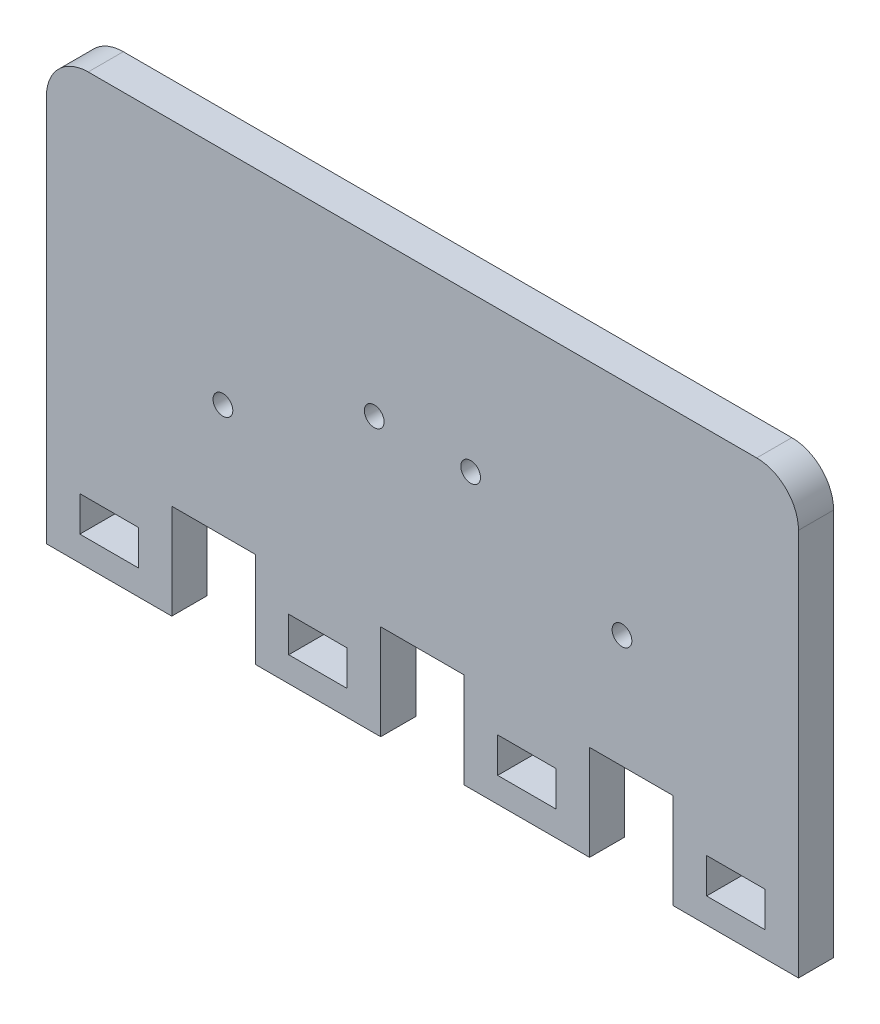
SolidWorks part; units mm, degrees
material "Teak"
ref_plane "Front Plane" through (0, 0, 0) normal (0, 0, 1) x (1, 0, 0)
ref_plane "Top Plane" through (0, 0, 0) normal (0, 1, 0) x (1, 0, 0)
ref_plane "Right Plane" through (0, 0, 0) normal (1, 0, 0) x (0, 0, -1)
sketch "Sketch1" plane through (0, 0, 0) normal (0, 0, 1) x (1, 0, 0)
  line L1 (-30.5325, 25.3111) -> (83.7675, 25.3111)
  line L2 (-30.5325, 25.3111) -> (-30.5325, -30.8229)
  line L3 (-30.5325, -30.8229) -> (83.7675, -30.8229)
  line L4 (83.7675, 25.3111) -> (83.7675, -30.8229)
  dimension "D1" = 56.134
  dimension "D2" = 114.3
extrude "Boss-Extrude1" add sketch "Sketch1" along normal blind 5.334 contours L1 L4 L3 L2
sketch "Sketch2" plane through (0, 0, 5.334) normal (0, 0, 1) x (1, 0, 0)
  line L0 (-30.5325, -30.8229) -> (83.7675, -30.8229) construction
  line L1 (-11.4825, -30.8229) -> (1.2175, -30.8229)
  line L2 (-11.4825, -30.8229) -> (-11.4825, -25.4889)
  line L3 (-11.4825, -25.4889) -> (1.2175, -25.4889)
  line L4 (1.2175, -30.8229) -> (1.2175, -25.4889)
  line L5 (-11.4825, -25.4889) -> (-30.5325, -25.4889) construction
  line L6 (20.2675, -30.8229) -> (32.9675, -30.8229)
  line L7 (20.2675, -30.8229) -> (20.2675, -25.4889)
  line L8 (20.2675, -25.4889) -> (32.9675, -25.4889)
  line L9 (32.9675, -30.8229) -> (32.9675, -25.4889)
  line L10 (52.0175, -30.8229) -> (64.7175, -30.8229)
  line L11 (52.0175, -30.8229) -> (52.0175, -25.4889)
  line L12 (52.0175, -25.4889) -> (64.7175, -25.4889)
  line L13 (64.7175, -30.8229) -> (64.7175, -25.4889)
  line L14 (-30.5325, 25.3111) -> (-30.5325, -30.8229) construction
  line L15 (1.2175, -25.4889) -> (20.2675, -25.4889) construction
  line L16 (32.9675, -25.4889) -> (52.0175, -25.4889) construction
  line L17 (64.7175, -25.4889) -> (83.7675, -25.4889) construction
  line L18 (83.7675, 25.3111) -> (83.7675, -30.8229) construction
  dimension "D1" = 19.05
  dimension "D3" = 19.05
  dimension "D5" = 19.05
  dimension "D6" = 12.7
  dimension "D7" = 19.05
  dimension "D8" = 5.334
extrude "Cut-Extrude1" cut sketch "Sketch2" against normal through all
fillet "Fillet1" radius 6.35 2 edges at (83.7675, 25.3111, 2.667) (-30.5325, 25.3111, 2.667)
sketch "Sketch3" plane through (0, 0, 0) normal (0, 0, -1) x (-1, 0, 0)
  line L16 (24.1825, 25.3111) -> (-77.4175, 25.3111)
  line L17 (-83.7675, 18.9611) -> (-83.7675, -30.8229)
  line L18 (-83.7675, -30.8229) -> (-64.7175, -30.8229)
  line L19 (-64.7175, -30.8229) -> (-64.7175, -25.4889)
  line L20 (-64.7175, -25.4889) -> (-52.0175, -25.4889)
  line L21 (-52.0175, -25.4889) -> (-52.0175, -30.8229)
  line L22 (-52.0175, -30.8229) -> (-32.9675, -30.8229)
  line L23 (-32.9675, -30.8229) -> (-32.9675, -25.4889)
  line L24 (-32.9675, -25.4889) -> (-20.2675, -25.4889)
  line L25 (-20.2675, -25.4889) -> (-20.2675, -30.8229)
  line L26 (-20.2675, -30.8229) -> (-1.2175, -30.8229)
  line L27 (-1.2175, -30.8229) -> (-1.2175, -25.4889)
  line L28 (-1.2175, -25.4889) -> (11.4825, -25.4889)
  line L29 (11.4825, -25.4889) -> (11.4825, -30.8229)
  line L30 (11.4825, -30.8229) -> (30.5325, -30.8229)
  line L31 (30.5325, -30.8229) -> (30.5325, 18.9611)
  line L32 (24.1825, 25.3111) -> (-77.4175, 25.3111)
  line L33 (-83.7675, 18.9611) -> (-83.7675, -30.8229)
  line L34 (-83.7675, -30.8229) -> (-64.7175, -30.8229)
  line L35 (-64.7175, -30.8229) -> (-64.7175, -25.4889)
  line L36 (-64.7175, -25.4889) -> (-52.0175, -25.4889)
  line L37 (-52.0175, -25.4889) -> (-52.0175, -30.8229)
  line L38 (-52.0175, -30.8229) -> (-32.9675, -30.8229)
  line L39 (-32.9675, -30.8229) -> (-32.9675, -25.4889)
  line L40 (-32.9675, -25.4889) -> (-20.2675, -25.4889)
  line L41 (-20.2675, -25.4889) -> (-20.2675, -30.8229)
  line L42 (-20.2675, -30.8229) -> (-1.2175, -30.8229)
  line L43 (-1.2175, -30.8229) -> (-1.2175, -25.4889)
  line L44 (-1.2175, -25.4889) -> (11.4825, -25.4889)
  line L45 (11.4825, -25.4889) -> (11.4825, -30.8229)
  line L46 (11.4825, -30.8229) -> (30.5325, -30.8229)
  line L47 (30.5325, -30.8229) -> (30.5325, 18.9611)
  line L48 (-83.7675, 18.9611) -> (-83.7675, -30.8229)
  line L49 (24.1825, 25.3111) -> (-77.4175, 25.3111)
  line L50 (30.5325, -30.8229) -> (30.5325, 18.9611)
  line L51 (11.4825, -30.8229) -> (30.5325, -30.8229)
  line L52 (11.4825, -25.4889) -> (11.4825, -30.8229)
  line L53 (-1.2175, -25.4889) -> (11.4825, -25.4889)
  line L54 (-1.2175, -30.8229) -> (-1.2175, -25.4889)
  line L55 (-20.2675, -30.8229) -> (-1.2175, -30.8229)
  line L56 (-20.2675, -25.4889) -> (-20.2675, -30.8229)
  line L57 (-32.9675, -25.4889) -> (-20.2675, -25.4889)
  line L58 (-32.9675, -30.8229) -> (-32.9675, -25.4889)
  line L59 (-52.0175, -30.8229) -> (-32.9675, -30.8229)
  line L60 (-52.0175, -25.4889) -> (-52.0175, -30.8229)
  line L61 (-64.7175, -25.4889) -> (-52.0175, -25.4889)
  line L62 (-64.7175, -30.8229) -> (-64.7175, -25.4889)
  line L63 (-83.7675, -30.8229) -> (-64.7175, -30.8229)
  line L64 (-83.7675, 18.9611) -> (-83.7675, -30.8229)
  line L65 (24.1825, 25.3111) -> (-77.4175, 25.3111)
  line L66 (30.5325, -30.8229) -> (30.5325, 18.9611)
  line L67 (11.4825, -30.8229) -> (30.5325, -30.8229)
  line L68 (11.4825, -25.4889) -> (11.4825, -30.8229)
  line L69 (-1.2175, -25.4889) -> (11.4825, -25.4889)
  line L70 (-1.2175, -30.8229) -> (-1.2175, -25.4889)
  line L71 (-20.2675, -30.8229) -> (-1.2175, -30.8229)
  line L72 (-20.2675, -25.4889) -> (-20.2675, -30.8229)
  line L73 (-32.9675, -25.4889) -> (-20.2675, -25.4889)
  line L74 (-32.9675, -30.8229) -> (-32.9675, -25.4889)
  line L75 (-52.0175, -30.8229) -> (-32.9675, -30.8229)
  line L76 (-52.0175, -25.4889) -> (-52.0175, -30.8229)
  line L77 (-64.7175, -25.4889) -> (-52.0175, -25.4889)
  line L78 (-64.7175, -30.8229) -> (-64.7175, -25.4889)
  line L79 (-83.7675, -30.8229) -> (-64.7175, -30.8229)
  circle A0 centre (3.7085, -8.2649) radius 1.5 construction
  circle A1 centre (-19.2915, 1.7351) radius 1.5 construction
  arc A2 (-77.4175, 25.3111) -> (-83.7675, 18.9611) centre (-77.4175, 18.9611) ccw
  arc A3 (30.5325, 18.9611) -> (24.1825, 25.3111) centre (24.1825, 18.9611) ccw
  arc A4 (-77.4175, 25.3111) -> (-83.7675, 18.9611) centre (-77.4175, 18.9611) ccw
  arc A5 (30.5325, 18.9611) -> (24.1825, 25.3111) centre (24.1825, 18.9611) ccw
  arc A6 (-77.4175, 25.3111) -> (-83.7675, 18.9611) centre (-77.4175, 18.9611) ccw
  arc A7 (30.5325, 18.9611) -> (24.1825, 25.3111) centre (24.1825, 18.9611) ccw
  arc A8 (-77.4175, 25.3111) -> (-83.7675, 18.9611) centre (-77.4175, 18.9611) ccw
  arc A9 (30.5325, 18.9611) -> (24.1825, 25.3111) centre (24.1825, 18.9611) ccw
  circle A10 centre (-56.9435, -8.2649) radius 1.5 construction
  circle A11 centre (-33.9435, 1.7351) radius 1.5 construction
  circle A12 centre (3.7085, -8.2649) radius 1.5
  circle A13 centre (-19.2915, 1.7351) radius 1.5
  circle A14 centre (-56.9435, -8.2649) radius 1.5
  circle A15 centre (-33.9435, 1.7351) radius 1.5
  dimension "D1" = 0
  dimension "D2" = 0
extrude "Cut-Extrude2" cut sketch "Sketch3" against normal through all contours A12 | A13 | A14 | A15
sketch "Sketch4" plane through (0, -30.8229, 0) normal (0, -1, 0) x (-1, 0, 0)
  line L0 (-1.2175, -5.334) -> (-20.2675, -5.334)
  line L1 (30.5325, -5.334) -> (11.4825, -5.334)
  line L2 (30.5325, -5.334) -> (30.5325, 0)
  line L3 (30.5325, 0) -> (11.4825, 0)
  line L4 (11.4825, -5.334) -> (11.4825, 0)
  line L5 (-1.2175, 0) -> (-20.2675, 0)
  line L6 (-20.2675, -5.334) -> (-20.2675, 0)
  line L7 (-1.2175, -5.334) -> (-1.2175, 0)
  line L8 (-32.9675, -5.334) -> (-52.0175, -5.334)
  line L9 (-32.9675, 0) -> (-52.0175, 0)
  line L10 (-52.0175, -5.334) -> (-52.0175, 0)
  line L11 (-32.9675, -5.334) -> (-32.9675, 0)
  line L12 (-64.7175, -5.334) -> (-83.7675, -5.334)
  line L13 (-64.7175, 0) -> (-83.7675, 0)
  line L14 (-83.7675, -5.334) -> (-83.7675, 0)
  line L15 (-64.7175, -5.334) -> (-64.7175, 0)
  dimension "D1" = 4
extrude "Boss-Extrude2" add sketch "Sketch4" along normal blind 9.144
sketch "Sketch6" plane through (0, 0, 5.334) normal (0, 0, 1) x (1, 0, 0)
  line L0 (-30.5325, 18.9611) -> (-30.5325, -39.9669) construction
  line L1 (-25.4525, -30.8229) -> (-16.5625, -30.8229)
  line L2 (-25.4525, -30.8229) -> (-25.4525, -36.1569)
  line L3 (-25.4525, -36.1569) -> (-16.5625, -36.1569)
  line L4 (-16.5625, -30.8229) -> (-16.5625, -36.1569)
  line L5 (-11.4825, -25.4889) -> (-11.4825, -39.9669) construction
  line L6 (1.2175, -25.4889) -> (-11.4825, -25.4889) construction
  line L8 (-5.1325, -25.4889) -> (-5.1325, -40.5378) construction
  line L9 (26.6175, -25.4889) -> (26.6175, -46.02) construction
  line L10 (32.9675, -25.4889) -> (20.2675, -25.4889) construction
  line L11 (58.3675, -25.4889) -> (58.3675, -43.8079) construction
  line L12 (64.7175, -25.4889) -> (52.0175, -25.4889) construction
  line L13 (6.2975, -30.8229) -> (6.2975, -36.1569)
  line L14 (15.1875, -36.1569) -> (6.2975, -36.1569)
  line L15 (15.1875, -30.8229) -> (15.1875, -36.1569)
  line L16 (15.1875, -30.8229) -> (6.2975, -30.8229)
  line L17 (38.0475, -30.8229) -> (46.9375, -30.8229)
  line L18 (38.0475, -30.8229) -> (38.0475, -36.1569)
  line L19 (38.0475, -36.1569) -> (46.9375, -36.1569)
  line L20 (46.9375, -30.8229) -> (46.9375, -36.1569)
  line L21 (69.7975, -30.8229) -> (69.7975, -36.1569)
  line L22 (78.6875, -36.1569) -> (69.7975, -36.1569)
  line L23 (78.6875, -30.8229) -> (78.6875, -36.1569)
  line L24 (78.6875, -30.8229) -> (69.7975, -30.8229)
  dimension "D1" = 5.08
  dimension "D2" = 5.08
  dimension "D3" = 5.334
  dimension "D4" = 5.334
extrude "Cut-Extrude3" cut sketch "Sketch6" against normal through all
equation "\"MDF\"= .21in"
equation "\"Foamcore\"= .13in"
equation "\"Gmaterial\"= \"MDF\""
equation "\"D1@Sketch1\"=\"MDF\"+2"
equation "\"D1@Boss-Extrude1\"=\"MDF\""
equation "\"D8@Sketch2\"=\"MDF\""
equation "\"D3@Sketch6\"=\"MDF\""
equation "\"D4@Sketch6\"=\"MDF\""
